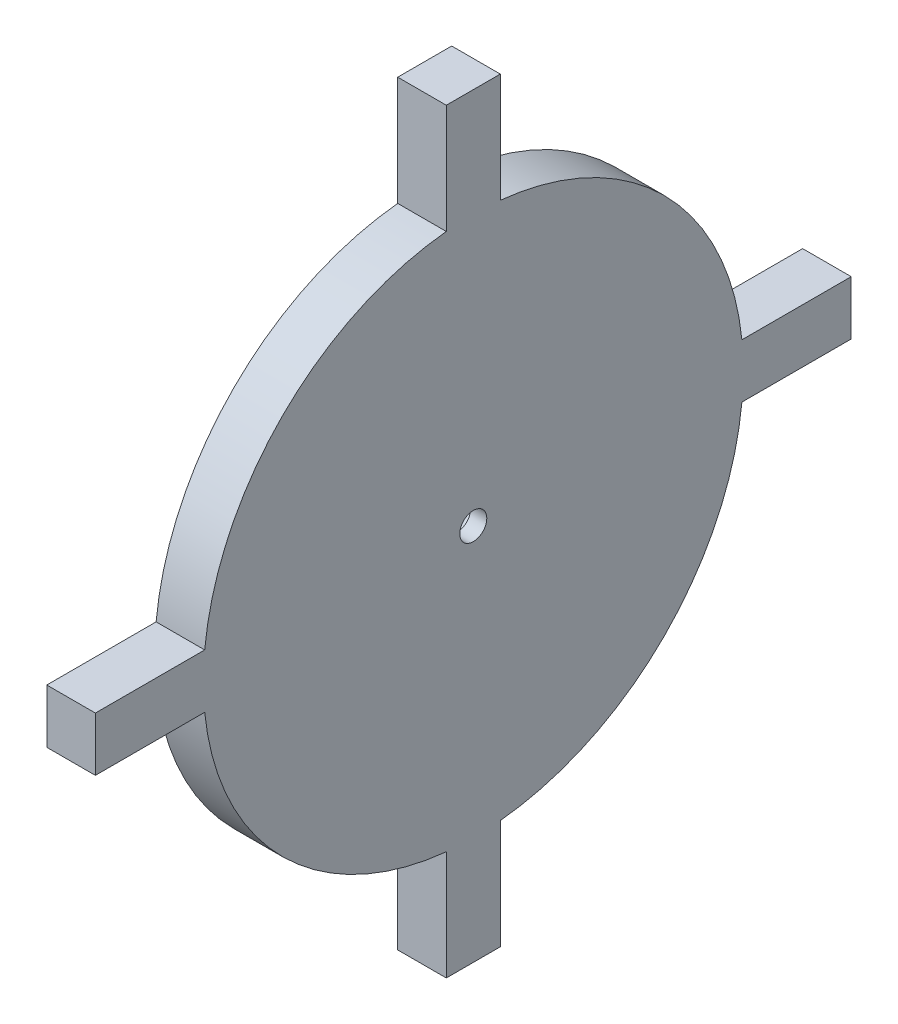
SolidWorks part; units mm, degrees
ref_plane "Front Plane" through (0, 0, 0) normal (0, 0, 1) x (1, 0, 0)
ref_plane "Top Plane" through (0, 0, 0) normal (0, 1, 0) x (1, 0, 0)
ref_plane "Right Plane" through (0, 0, 0) normal (1, 0, 0) x (0, 0, -1)
sketch "Sketch1" plane through (0, 0, 0) normal (1, 0, 0) x (0, 0, -1)
  line L1 (-6.35, 88.9) -> (6.35, 88.9)
  line L2 (-6.35, 88.9) -> (-6.35, -88.9)
  line L3 (-6.35, -88.9) -> (6.35, -88.9)
  line L4 (6.35, 88.9) -> (6.35, -88.9)
  line L5 (-6.35, 88.9) -> (6.35, -88.9) construction
  line L6 (-6.35, -88.9) -> (6.35, 88.9) construction
  line L7 (-88.9, -6.35) -> (88.9, -6.35)
  line L8 (-88.9, -6.35) -> (-88.9, 6.35)
  line L9 (-88.9, 6.35) -> (88.9, 6.35)
  line L10 (88.9, -6.35) -> (88.9, 6.35)
  line L11 (-88.9, -6.35) -> (88.9, 6.35) construction
  line L12 (-88.9, 6.35) -> (88.9, -6.35) construction
  circle A0 centre (0, 0) radius 63.5
  circle A1 centre (0, 0) radius 3.175
  dimension "D1" = 127
  dimension "D6" = 6.35
  dimension "D2" = 12.7
  dimension "D3" = 12.7
  dimension "D4" = 177.8
  dimension "D5" = 177.8
extrude "Boss-Extrude1" add sketch "Sketch1" along normal blind 11.43 contours L9 A0 L4 | A0 L4 L1 L2 | L4 A0 L2 L9 | L2 A0 L9 | A0 L9 L8 L7 | L9 A0 L7 L2 | L7 A0 L2 | L4 A0 L7 | L7 A0 L9 L4 | A0 L7 L10 L9 | L9 L2 L7 L4 | L2 A0 L4 L7 | A0 L2 L3 L4 region at (0, 76.1468, 0) region at (0, 34.8721, 0) region at (0, 29.7404, 29.7404) region at (0, 29.7404, -29.7404) region at (0, 6.1704, 0) region at (0, 0, 34.8721) region at (0, 0, 76.1468) region at (0, 0, -34.8721) region at (0, 0, -76.1468) region at (0, -34.8721, 0) region at (0, -29.7404, 29.7404) region at (0, -29.7404, -29.7404) region at (0, -76.1468, 0)
sketch "Sketch2" plane through (0, 0, 0) normal (-1, 0, 0) x (0, 0, 1)
  line L1 (-9.7282, -0.9706) -> (-4.0235, -8.9101)
  line L2 (-4.0235, -8.9101) -> (5.7046, -7.9395)
  line L3 (5.7046, -7.9395) -> (9.7282, 0.9706)
  line L4 (9.7282, 0.9706) -> (4.0235, 8.9101)
  line L5 (4.0235, 8.9101) -> (-5.7046, 7.9395)
  line L6 (-5.7046, 7.9395) -> (-9.7282, -0.9706)
  circle A0 centre (0, 0) radius 9.7765
  circle A1 centre (0, 0) radius 8.4667 construction
  dimension "D1" = 16.9333
extrude "Cut-Extrude1" cut sketch "Sketch2" against normal blind 7.62 contours A0
